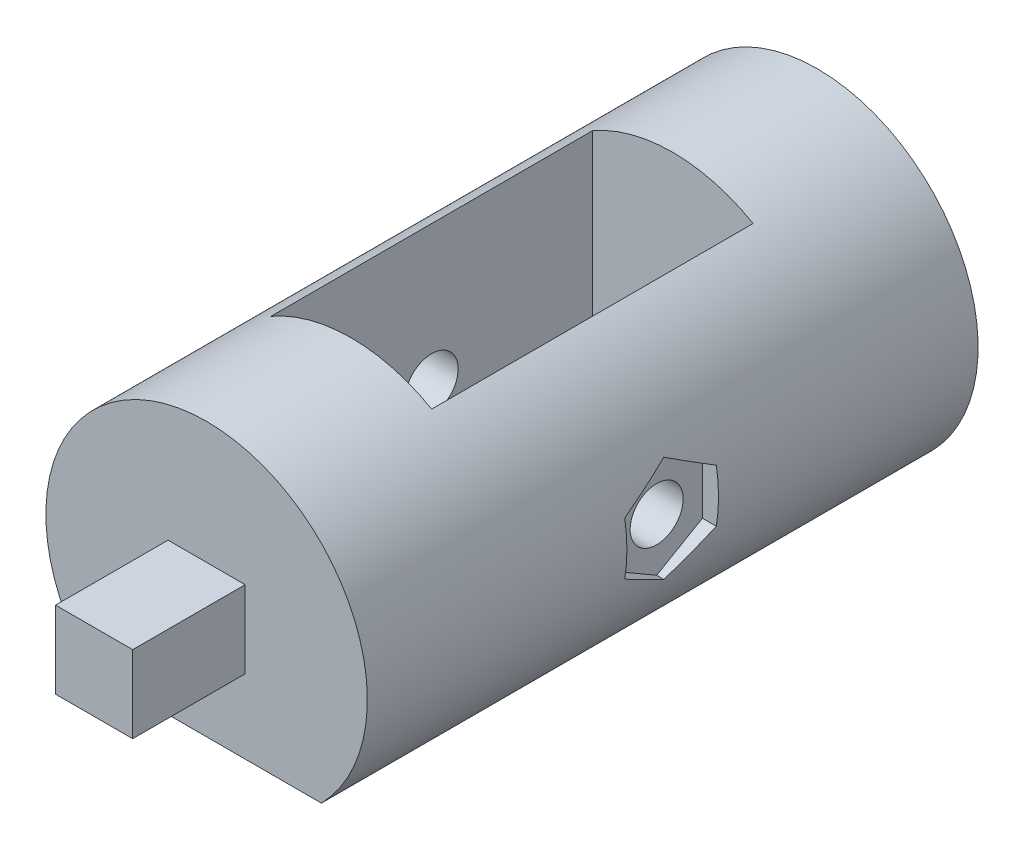
SolidWorks part; units mm, degrees
ref_plane "Ebene vorne" through (0, 0, 0) normal (0, 0, 1) x (1, 0, 0)
ref_plane "Ebene oben" through (0, 0, 0) normal (0, 1, 0) x (1, 0, 0)
ref_plane "Ebene rechts" through (0, 0, 0) normal (1, 0, 0) x (0, 0, -1)
sketch "Skizze1" plane through (0, 0, 0) normal (0, 0, 1) x (1, 0, 0)
  circle A0 centre (0, 0) radius 10
  dimension "D1" = 20
extrude "Aufsatz-Linear austragen1" add sketch "Skizze1" along normal blind 38
sketch "Skizze2" plane through (0, 0, 38) normal (0, 0, 1) x (1, 0, 0)
  line L1 (-2.4, 2.4) -> (2.4, 2.4)
  line L2 (-2.4, 2.4) -> (-2.4, -2.4)
  line L3 (-2.4, -2.4) -> (2.4, -2.4)
  line L4 (2.4, 2.4) -> (2.4, -2.4)
extrude "Aufsatz-Linear austragen2" add sketch "Skizze2" along normal blind 7
sketch "Skizze3" plane through (0, 0, 0) normal (0, 0, -1) x (-1, 0, 0)
  line L0 (-2.1846, 1.5) -> (2.1846, 1.5)
  circle A0 centre (0, 0) radius 2.65
  dimension "D1" = 1.5
  dimension "D2" = 5.3
extrude "Schnitt-Linear austragen1" cut sketch "Skizze3" against normal blind 7 contours L0 A0 region at (0, -0.375, 0)
sketch "Skizze4" plane through (0, 0, 0) normal (0, 0, -1) x (-1, 0, 0)
  line L1 (10, -14) -> (-10, -14)
  line L2 (10, -14) -> (10, -7)
  line L3 (10, -7) -> (-10, -7)
  line L4 (-10, -14) -> (-10, -7)
  dimension "D1" = 10
  dimension "D2" = 10
  dimension "D3" = 7
  dimension "D4" = 7
extrude "Schnitt-Linear austragen3" cut sketch "Skizze4" against normal up to surface (38 mm away) contours L2 L3 L4 L1 up to face at (10, 0, 38)
sketch "Skizze5" plane through (0, -7, 0) normal (0, -1, 0) x (1, 0, 0)
  line L0 (-10, 0) -> (10, 0) construction
  line L1 (-5, 29) -> (5, 29)
  line L2 (-5, 29) -> (-5, 9)
  line L3 (-5, 9) -> (5, 9)
  line L4 (5, 29) -> (5, 9)
  dimension "D1" = 5
  dimension "D2" = 5
  dimension "D3" = 20
  dimension "D4" = 9
extrude "Schnitt-Linear austragen4" cut sketch "Skizze5" against normal up to next contours L2 L3 L4 L1
sketch "Skizze6" plane through (5, 0, 0) normal (-1, 0, 0) x (0, 0, 1)
  line L0 (9, 10) -> (0, 10) construction
  line L1 (0, 10) -> (0, -7) construction
  circle A0 centre (19, 0) radius 1.65
  dimension "D1" = 3.3
  dimension "D2" = 10
  dimension "D3" = 19
extrude "Schnitt-Linear austragen5" cut sketch "Skizze6" against normal through all and the other way through all
sketch "Skizze7" plane through (5, 0, 0) normal (-1, 0, 0) x (0, 0, 1)
  line L1 (19, -3.2909) -> (21.85, -1.6454)
  line L2 (21.85, -1.6454) -> (21.85, 1.6454)
  line L3 (21.85, 1.6454) -> (19, 3.2909)
  line L4 (19, 3.2909) -> (16.15, 1.6454)
  line L5 (16.15, 1.6454) -> (16.15, -1.6454)
  line L6 (16.15, -1.6454) -> (19, -3.2909)
  circle A0 centre (19, 0) radius 2.85 construction
  dimension "D1" = 5.7
extrude "Schnitt-Linear austragen6" cut sketch "Skizze7" against normal up to surface (0.8637 mm away) from offset 4 up to face at (9.9937, 0.3544, 20.6115) offset against normal yes
extrude "Schnitt-Linear austragen7" cut sketch "Skizze7<2>" along normal up to surface (0.8637 mm away) from offset 14 up to face at (9.7922, 0, 19)
sketch "Skizze7<2>" plane through (5, 0, 0) normal (-1, 0, 0) x (0, 0, 1) same geometry as "Skizze7"
